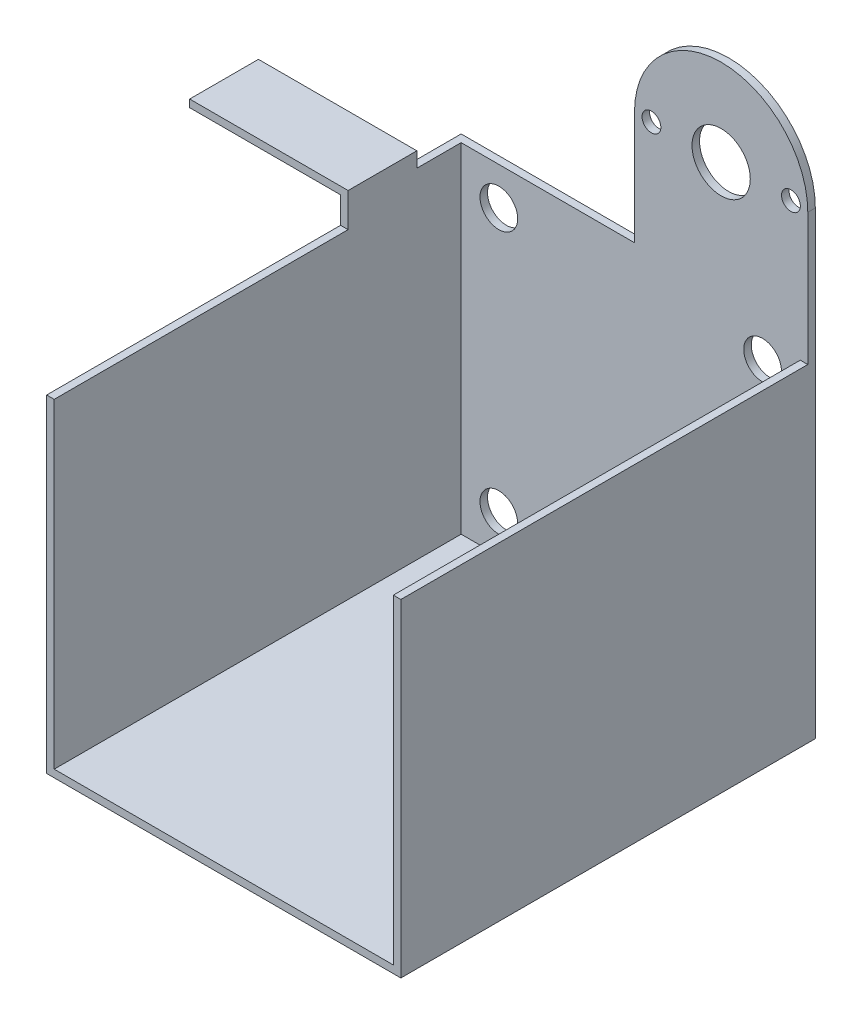
SolidWorks part; units mm, degrees
ref_plane "Front Plane" through (0, 0, 0) normal (0, 0, 1) x (1, 0, 0)
ref_plane "Top Plane" through (0, 0, 0) normal (0, 1, 0) x (1, 0, 0)
ref_plane "Right Plane" through (0, 0, 0) normal (1, 0, 0) x (0, 0, -1)
sketch "Sketch1" plane through (0, 0, 0) normal (0, 0, 1) x (1, 0, 0)
  line L14 (-73.3408, 141.3496) -> (-73.3408, 21.3496)
  line L15 (-73.3408, 21.3496) -> (-119.3408, 21.3496)
  line L16 (-119.3408, 111.3496) -> (-119.3408, 141.3496)
  line L17 (-119.3408, 21.3496) -> (-165.3408, 21.3496)
  line L19 (-165.3408, 31.3496) -> (-165.3408, 111.3496)
  line L20 (-165.3408, 111.3496) -> (-119.3408, 111.3496)
  line L21 (-155.3408, 111.3496) -> (-85.3408, 111.3496) construction
  line L22 (-165.3408, 31.3496) -> (-165.3408, 21.3496)
  arc A1 (-73.3408, 141.3496) -> (-119.3408, 141.3496) centre (-96.3408, 141.3496) ccw
  circle A2 centre (-96.3408, 141.3496) radius 7.7362
  circle A3 centre (-85.3408, 101.3496) radius 5
  circle A4 centre (-77.8196, 141.7855) radius 2.5
  circle A5 centre (-114.8408, 141.3496) radius 2.5
  circle A6 centre (-155.3408, 101.3496) radius 5
  circle A7 centre (-85.3408, 31.3496) radius 5
  circle A8 centre (-155.3408, 31.3496) radius 5
  point P4 (0, 0)
  dimension "D3" = 5
  dimension "D4" = 5
  dimension "D2" = 120
  dimension "D5" = 4.5
  dimension "D6" = 4.5
  dimension "D7" = 0
extrude "Boss-Extrude1" add sketch "Sketch1" along normal blind 2
sketch "Sketch2" plane through (0, 0, 0) normal (0, 1, 0) x (1, 0, 0)
  line L18 (-165.3408, 0) -> (-165.3408, -110)
  line L20 (-73.3408, -110) -> (-165.3408, -110)
  line L21 (-73.3408, 0) -> (-73.3408, -110)
  line L22 (-73.3408, 0) -> (-165.3408, 0)
ref_plane "Plane1" through (-73.3408, 0, 0) normal (1, 0, 0) x (0, 0, -1)
extrude "Boss-Extrude4" add sketch "Sketch2" against normal blind 2 from surface separate body starting at face at (-119.3408, 21.3496, 1)
sketch "Sketch4" plane through (-73.3408, 0, 0) normal (1, 0, 0) x (0, 0, -1)
  line L1 (0, 19.3496) -> (-110, 19.3496)
  line L2 (0, 19.3496) -> (0, 106.3496)
  line L3 (0, 106.3496) -> (-110, 106.3496)
  line L4 (-110, 19.3496) -> (-110, 106.3496)
extrude "Boss-Extrude5" add sketch "Sketch4" against normal blind 2
sketch "Sketch5" plane through (0, 0, 0) normal (1, 0, 0) x (0, 0, -1)
  line L1 (0, 19.3496) -> (-110, 19.3496)
  line L2 (0, 19.3496) -> (0, 106.3496)
  line L4 (-110, 19.3496) -> (-110, 106.3496)
  line L6 (-32, 115.3496) -> (-32, 106.3496)
  line L7 (-32, 106.3496) -> (-110, 106.3496)
  line L9 (0, 111.3496) -> (0, 106.3496)
  line L12 (-13.75, 115.3496) -> (-13.75, 111.3496)
  line L13 (-13.75, 111.3496) -> (0, 111.3496)
  line L14 (-13.75, 115.3496) -> (-32, 115.3496)
  line L15 (-38, 115.3496) -> (-13.75, 115.3496) construction
extrude "Boss-Extrude6" add sketch "Sketch5" against normal blind 2 from surface starting at face at (-165.3408, 50.683, 37.3333)
sketch "Sketch7" plane through (0, 0, 0) normal (0, 1, 0) x (1, 0, 0)
  line L0 (-165.3408, -13.75) -> (-207.3873, -13.75)
  line L1 (-1044.6803, -13.75) -> (-130.2803, -13.75) construction
  line L2 (-207.3873, -13.75) -> (-207.3873, -32)
  line L3 (-1044.6803, -32) -> (-130.2803, -32) construction
  line L4 (-207.3873, -32) -> (-165.3408, -32)
  line L5 (-165.3408, -32) -> (-165.3408, -13.75)
extrude "Boss-Extrude8" add sketch "Sketch7" against normal blind 2 from surface starting at face at (-166.3408, 115.3496, 22.875)
